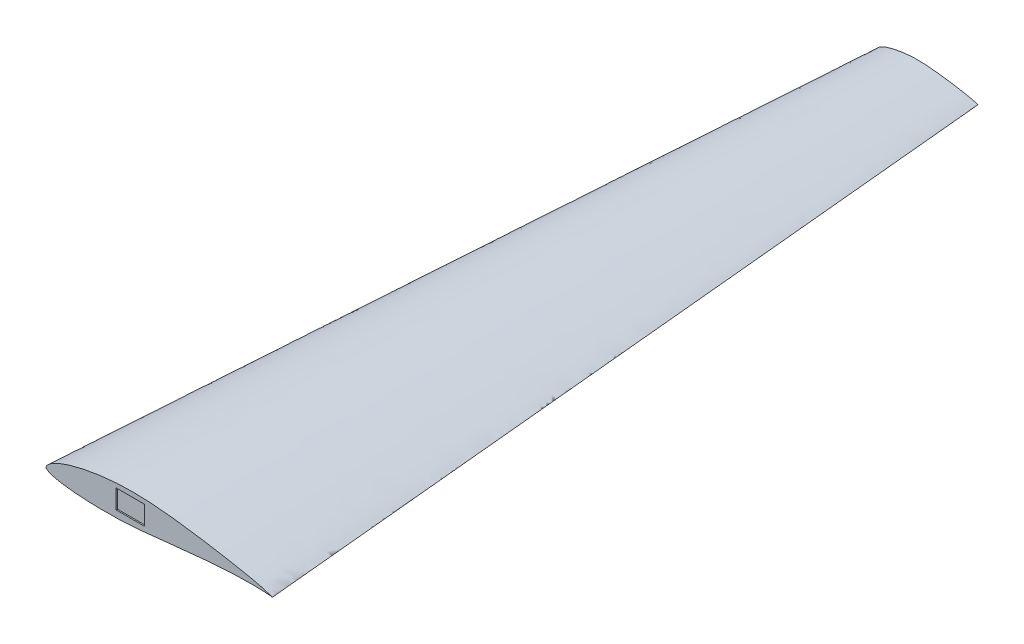
SolidWorks part; units mm, degrees
ref_plane "Front Plane" through (0, 0, 0) normal (0, 0, 1) x (1, 0, 0)
ref_plane "Top Plane" through (0, 0, 0) normal (0, 1, 0) x (1, 0, 0)
ref_plane "Right Plane" through (0, 0, 0) normal (1, 0, 0) x (0, 0, -1)
curve "Curve1"
  spline degree 3 poles (0.9921, 0.0008, 0) (1.0019, -0.0008, 0) (0.9929, 0.0016, 0) (0.9861, 0.0043, 0) (0.9706, 0.0096, 0) (0.9519, 0.0152, 0) (0.9278, 0.021, 0) (0.8992, 0.0273, 0) (0.8662, 0.0341, 0) (0.8293, 0.0413, 0) (0.789, 0.0488, 0) (0.746, 0.0564, 0) (0.7007, 0.0641, 0) (0.6538, 0.0714, 0) (0.6058, 0.0784, 0) (0.5573, 0.0846, 0) (0.5088, 0.0898, 0) (0.4609, 0.0938, 0) (0.4138, 0.0961, 0) (0.3679, 0.0966, 0) (0.3232, 0.0952, 0) (0.2801, 0.092, 0) (0.2388, 0.0874, 0) (0.1997, 0.0815, 0) (0.1631, 0.0746, 0) (0.1296, 0.0669, 0) (0.0993, 0.0585, 0) (0.0726, 0.0496, 0) (0.0499, 0.0404, 0) (0.0312, 0.031, 0) (0.0168, 0.0217, 0) (0.0085, 0.0145, 0) (0.0039, 0.009, 0) (0.0018, 0.0058, 0) (0.0004, 0.0024, 0) (0, 0.0003, 0) (0, -0.0012, 0) (0.0006, -0.0026, 0) (0.002, -0.0043, 0) (0.0049, -0.007, 0) (0.0107, -0.0108, 0) (0.0215, -0.0156, 0) (0.0378, -0.0206, 0) (0.0598, -0.0253, 0) (0.0864, -0.0294, 0) (0.1174, -0.033, 0) (0.1523, -0.036, 0) (0.1908, -0.0383, 0) (0.2323, -0.0397, 0) (0.2764, -0.0402, 0) (0.3228, -0.0395, 0) (0.3711, -0.0373, 0) (0.4212, -0.0335, 0) (0.4729, -0.0284, 0) (0.526, -0.0227, 0) (0.5798, -0.0169, 0) (0.6336, -0.0114, 0) (0.6866, -0.0064, 0) (0.7378, -0.0023, 0) (0.7866, 0.0009, 0) (0.832, 0.0031, 0) (0.8733, 0.0042, 0) (0.9096, 0.0045, 0) (0.9406, 0.0038, 0) (0.9645, 0.0029, 0) (0.984, 0.0013, 0) (0.9921, 0.0008, 0) (1.0019, -0.0008, 0) (0.9929, 0.0016, 0) knots -0.016161 -0.007282 -0.001839 0 0.00178 0.006777 0.014308 0.024046 0.036116 0.050547 0.06713 0.085624 0.105767 0.127282 0.149864 0.17323 0.197069 0.221103 0.245052 0.268663 0.291773 0.314299 0.336178 0.357377 0.377792 0.397225 0.415489 0.432417 0.447849 0.461651 0.473687 0.483898 0.492263 0.498797 0.499955 0.502811 0.504371 0.50536 0.505925 0.506503 0.507535 0.509205 0.512345 0.517665 0.526422 0.537425 0.550643 0.565966 0.583206 0.602155 0.622587 0.644255 0.666998 0.690703 0.715307 0.740824 0.767084 0.793717 0.820331 0.846519 0.871863 0.895937 0.918335 0.938667 0.956573 0.971715 0.983839 0.992718 0.998161 1 1.00178 1.006777 1.014308 periodic
sketch "Sketch1" plane through (0, 0, 0) normal (0, 0, 1) x (1, 0, 0)
  line L0 (637.2059, -30.8288) -> (-1162.7941, -35.0845) construction
  spline S1 degree 3 poles (622.967, -28.64) (640.692, -31.5786) (624.3406, -27.283) (612.1808, -22.4384) (584.1935, -12.9236) (550.5734, -3.0031) (507.0318, 7.3176) (455.5452, 18.4128) (396.0453, 30.4121) (329.6088, 43.1368) (257.1037, 56.3698) (179.566, 69.8812) (98.004, 83.2872) (13.4916, 96.2742) (-72.9444, 108.4165) (-160.2766, 119.2439) (-247.5248, 128.3611) (-333.8508, 135.2066) (-418.6228, 139.0501) (-501.3609, 139.671) (-581.7163, 136.8854) (-659.2966, 130.868) (-733.6064, 122.2205) (-804.0052, 111.4712) (-869.743, 98.8183) (-930.1494, 84.6626) (-984.6043, 69.3092) (-1032.5261, 53.0959) (-1073.4471, 36.3919) (-1106.9728, 19.4367) (-1132.8144, 2.6523) (-1147.698, -10.4496) (-1155.9379, -20.4072) (-1159.736, -26.142) (-1162.2969, -32.2888) (-1163.0296, -36.0635) (-1162.8865, -38.7086) (-1161.8222, -41.1954) (-1159.3385, -44.3902) (-1154.0434, -49.2445) (-1143.5465, -55.9865) (-1124.1742, -64.4963) (-1094.6997, -73.385) (-1055.1419, -81.7565) (-1007.2196, -89.0072) (-951.47, -95.2724) (-888.5578, -100.3967) (-819.2858, -104.233) (-744.5209, -106.6291) (-665.0686, -107.2277) (-581.6186, -105.541) (-494.6577, -101.2591) (-404.4744, -94.1471) (-311.3767, -84.5976) (-215.8933, -74.0273) (-119.0803, -63.2443) (-22.3001, -52.9711) (72.9936, -43.6696) (165.2978, -35.8585) (253.0846, -29.787) (334.8123, -25.5512) (409.125, -23.2681) (474.3717, -22.626) (530.1728, -23.5565) (573.2061, -25.0278) (608.3968, -27.7924) (622.967, -28.64) (640.692, -31.5786) (624.3406, -27.283) knots -0.016161 -0.007282 -0.001839 0 0.00178 0.006777 0.014308 0.024046 0.036116 0.050547 0.06713 0.085624 0.105767 0.127282 0.149864 0.17323 0.197069 0.221103 0.245052 0.268663 0.291773 0.314299 0.336178 0.357377 0.377792 0.397225 0.415489 0.432417 0.447849 0.461651 0.473687 0.483898 0.492263 0.498797 0.499955 0.502811 0.504371 0.50536 0.505925 0.506503 0.507535 0.509205 0.512345 0.517665 0.526422 0.537425 0.550643 0.565966 0.583206 0.602155 0.622587 0.644255 0.666998 0.690703 0.715307 0.740824 0.767084 0.793717 0.820331 0.846519 0.871863 0.895937 0.918335 0.938667 0.956573 0.971715 0.983839 0.992718 0.998161 1 1.00178 1.006777 1.014308 only from (637.2059, -30.8288) to (637.2059, -30.8288)
  dimension "D1" = 1800
ref_plane "Plane1" through (0, 0, 6200) normal (0, 0, 1) x (1, 0, 0)
ref_plane "Plane3" through (0, -35.0845, 0) normal (0, 1, 0) x (1, 0, 0)
sketch "Sketch4" plane through (0, -35.0845, 0) normal (0, 1, 0) x (1, 0, 0)
  line L1 (637.2059, 0) -> (-1162.7941, 0) construction
  line L2 (-172.1886, -6200) -> (172.1886, -6200) construction
  line L4 (-1162.7941, 0) -> (-862.7941, -6200)
sketch "Sketch5" plane through (0, 0, 6200) normal (0, 0, 1) x (1, 0, 0)
  line L0 (46.251, -35.2354) -> (-753.7688, -35.3009) construction
  spline S1 degree 3 poles (39.9103, -34.3504) (47.78, -35.5469) (40.5107, -33.741) (35.0952, -31.6671) (22.6402, -27.6181) (7.6874, -23.4229) (-11.663, -19.1093) (-34.5377, -14.4998) (-60.9677, -9.5373) (-90.4749, -4.2947) (-122.6736, 1.1372) (-157.1033, 6.6624) (-193.3153, 12.1171) (-230.8318, 17.3686) (-269.1955, 22.2345) (-307.9483, 26.5125) (-346.6538, 30.0335) (-384.9373, 32.5536) (-422.5145, 33.7529) (-459.1715, 33.5367) (-494.7528, 31.8256) (-529.0855, 28.6992) (-561.9538, 24.4271) (-593.0769, 19.2472) (-622.124, 13.2516) (-648.8002, 6.6219) (-672.8329, -0.5031) (-693.9662, -7.9701) (-711.9952, -15.6131) (-726.7466, -23.3233) (-738.0949, -30.9123) (-744.6106, -36.8049) (-748.2018, -41.2651) (-749.8503, -43.8282) (-750.9483, -46.5664) (-751.2505, -48.243) (-751.1714, -49.4139) (-750.6851, -50.5093) (-749.5659, -51.9099) (-747.1913, -54.0289) (-742.5011, -56.9533) (-733.8685, -60.6082) (-720.7584, -64.3709) (-703.1844, -67.8447) (-681.9116, -70.7722) (-657.1771, -73.2167) (-629.2762, -75.1133) (-598.5656, -76.4015) (-565.4302, -77.0191) (-530.2289, -76.8125) (-493.2702, -75.5698) (-454.7715, -73.1566) (-414.8621, -69.4706) (-373.6761, -64.6873) (-331.4393, -59.4377) (-288.6147, -54.086) (-245.8016, -48.9603) (-203.6413, -44.2739) (-162.7964, -40.2655) (-123.9425, -37.0546) (-87.7619, -34.6929) (-54.8546, -33.2402) (-25.9538, -32.5684) (-1.2281, -32.6493) (17.8446, -33.0456) (33.4506, -34.0614) (39.9103, -34.3504) (47.78, -35.5469) (40.5107, -33.741) knots -0.016161 -0.007282 -0.001839 0 0.00178 0.006777 0.014308 0.024046 0.036116 0.050547 0.06713 0.085624 0.105767 0.127282 0.149864 0.17323 0.197069 0.221103 0.245052 0.268663 0.291773 0.314299 0.336178 0.357377 0.377792 0.397225 0.415489 0.432417 0.447849 0.461651 0.473687 0.483898 0.492263 0.498797 0.499955 0.502811 0.504371 0.50536 0.505925 0.506503 0.507535 0.509205 0.512345 0.517665 0.526422 0.537425 0.550643 0.565966 0.583206 0.602155 0.622587 0.644255 0.666998 0.690703 0.715307 0.740824 0.767084 0.793717 0.820331 0.846519 0.871863 0.895937 0.918335 0.938667 0.956573 0.971715 0.983839 0.992718 0.998161 1 1.00178 1.006777 1.014308 only from (46.2312, -35.2354) to (46.2312, -35.2354)
  dimension "D1" = 800
sketch "Sketch6" plane through (0, 0, 6200) normal (0, 0, 1) x (1, 0, 0)
  line L0 (-753.7688, -35.3009) -> (-751.2083, -48.6103)
  spline S0 degree 3 poles (39.9103, -34.3504) (47.78, -35.5469) (40.5107, -33.741) (35.0952, -31.6671) (22.6402, -27.6181) (7.6874, -23.4229) (-11.663, -19.1093) (-34.5377, -14.4998) (-60.9677, -9.5373) (-90.4749, -4.2947) (-122.6736, 1.1372) (-157.1033, 6.6624) (-193.3153, 12.1171) (-230.8318, 17.3686) (-269.1955, 22.2345) (-307.9483, 26.5125) (-346.6538, 30.0335) (-384.9373, 32.5536) (-422.5145, 33.7529) (-459.1715, 33.5367) (-494.7528, 31.8256) (-529.0855, 28.6992) (-561.9538, 24.4271) (-593.0769, 19.2472) (-622.124, 13.2516) (-648.8002, 6.6219) (-672.8329, -0.5031) (-693.9662, -7.9701) (-711.9952, -15.6131) (-726.7466, -23.3233) (-738.0949, -30.9123) (-744.6106, -36.8049) (-748.2018, -41.2651) (-749.8503, -43.8282) (-750.9483, -46.5664) (-751.2505, -48.243) (-751.1714, -49.4139) (-750.6851, -50.5093) (-749.5659, -51.9099) (-747.1913, -54.0289) (-742.5011, -56.9533) (-733.8685, -60.6082) (-720.7584, -64.3709) (-703.1844, -67.8447) (-681.9116, -70.7722) (-657.1771, -73.2167) (-629.2762, -75.1133) (-598.5656, -76.4015) (-565.4302, -77.0191) (-530.2289, -76.8125) (-493.2702, -75.5698) (-454.7715, -73.1566) (-414.8621, -69.4706) (-373.6761, -64.6873) (-331.4393, -59.4377) (-288.6147, -54.086) (-245.8016, -48.9603) (-203.6413, -44.2739) (-162.7964, -40.2655) (-123.9425, -37.0546) (-87.7619, -34.6929) (-54.8546, -33.2402) (-25.9538, -32.5684) (-1.2281, -32.6493) (17.8446, -33.0456) (33.4506, -34.0614) (39.9103, -34.3504) (47.78, -35.5469) (40.5107, -33.741) knots -0.016161 -0.007282 -0.001839 0 0.00178 0.006777 0.014308 0.024046 0.036116 0.050547 0.06713 0.085624 0.105767 0.127282 0.149864 0.17323 0.197069 0.221103 0.245052 0.268663 0.291773 0.314299 0.336178 0.357377 0.377792 0.397225 0.415489 0.432417 0.447849 0.461651 0.473687 0.483898 0.492263 0.498797 0.499955 0.502811 0.504371 0.50536 0.505925 0.506503 0.507535 0.509205 0.512345 0.517665 0.526422 0.537425 0.550643 0.565966 0.583206 0.602155 0.622587 0.644255 0.666998 0.690703 0.715307 0.740824 0.767084 0.793717 0.820331 0.846519 0.871863 0.895937 0.918335 0.938667 0.956573 0.971715 0.983839 0.992718 0.998161 1 1.00178 1.006777 1.014308 only from (46.2312, -35.2354) to (46.2312, -35.2354) construction
ref_axis "Axis2" through (-751.2083, -48.6103, 6200) along (-0.0662, 0.0022, -0.9978)
loft "Loft5" add profiles "Sketch1", "Sketch5" connector at (-1162.9043, -36.0103, 0) connector at (-751.1274, -47.6465, 6200)
sketch "Sketch7" plane through (0, 0, 0) normal (0, 0, -1) x (-1, 0, 0)
  line L1 (378.6621, 100.8715) -> (605.0337, 100.8715)
  line L2 (378.6621, 100.8715) -> (378.6621, -50.9306)
  line L3 (378.6621, -50.9306) -> (605.0337, -50.9306)
  line L4 (605.0337, 100.8715) -> (605.0337, -50.9306)
extrude "Boss-Extrude1" add sketch "Sketch7" along normal blind 10
mirror "Mirror1" about plane through (0, 0, -10) normal (0, 0, -1) of bodies 110
sketch "Sketch9" plane through (0, 0, 0) normal (0, 0, -1) x (-1, 0, 0)
  line L1 (-815.2717, -249.2353) -> (1291.6317, -249.2353)
  line L2 (-815.2717, -249.2353) -> (-815.2717, 363.9065)
  line L3 (-815.2717, 363.9065) -> (1291.6317, 363.9065)
  line L4 (1291.6317, -249.2353) -> (1291.6317, 363.9065)
extrude "Cut-Extrude1" cut sketch "Sketch9" against normal blind 6969
sketch "Sketch10" plane through (0, 0, 0) normal (0, 0, 1) x (1, 0, 0)
  line L4 (-378.6621, -50.9306) -> (-378.6621, 100.8715)
  line L5 (-378.6621, 100.8715) -> (-605.0337, 100.8715)
  line L6 (-605.0337, 100.8715) -> (-605.0337, -50.9306)
  line L7 (-605.0337, -50.9306) -> (-378.6621, -50.9306)
  line L8 (-378.6621, -50.9306) -> (-378.6621, 100.8715)
  line L9 (-378.6621, 100.8715) -> (-605.0337, 100.8715)
  line L10 (-605.0337, 100.8715) -> (-605.0337, -50.9306)
  line L11 (-605.0337, -50.9306) -> (-378.6621, -50.9306)
  dimension "D1" = 0
extrude "Cut-Extrude2" cut sketch "Sketch10" against normal blind 30
